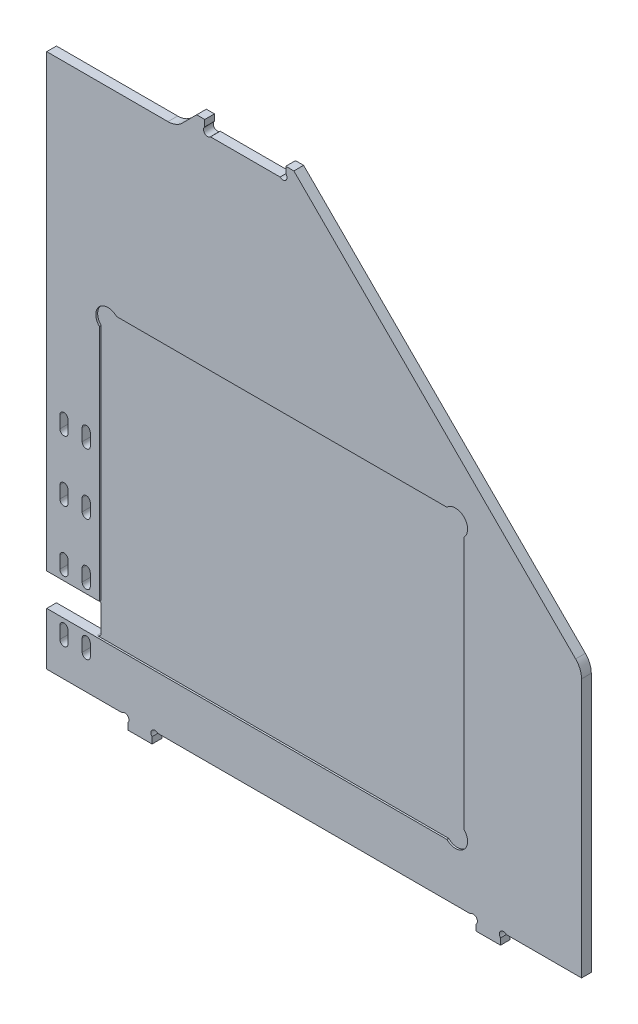
SolidWorks part; units mm, degrees
ref_plane "Front Plane" through (0, 0, 0) normal (0, 0, 1) x (1, 0, 0)
ref_plane "Top Plane" through (0, 0, 0) normal (0, 1, 0) x (1, 0, 0)
ref_plane "Right Plane" through (0, 0, 0) normal (1, 0, 0) x (0, 0, -1)
sketch "Sketch1" plane through (0, 0, 0) normal (0, 0, 1) x (1, 0, 0)
  line L2 (0, 66) -> (0, -66) construction
  line L3 (66, 66) -> (-66, 66)
  line L4 (66, 66) -> (66, -66)
  line L5 (66, -66) -> (-66, -66)
  line L6 (-66, 66) -> (-66, -66)
  line L7 (66, 66) -> (-66, -66) construction
  line L8 (66, -66) -> (-66, 66) construction
  line L9 (0, 66) -> (66, 0)
  line L10 (0, 66) -> (-7, 73)
  line L11 (-7, 73) -> (-27, 73)
  line L12 (-27, 73) -> (-34, 66)
  line L13 (-32, 68) -> (-2, 68)
  line L14 (39.2929, -66.7071) -> (40, -66) construction
  line L15 (46, -66) -> (40, -66)
  line L16 (46, -66) -> (46, -69)
  line L17 (46, -69) -> (40, -69)
  line L18 (40, -66) -> (40, -69)
  line L19 (43, -69) -> (43, -66) construction
  line L20 (-46, -66) -> (-46, -69)
  line L21 (-46, -66) -> (-40, -66)
  line L22 (-40, -66) -> (-40, -69)
  line L23 (-46, -69) -> (-40, -69)
  line L24 (-17, 73) -> (-17, 66) construction
  line L25 (-7, 71) -> (-5, 71)
  line L26 (-27, 71) -> (-7, 71)
  line L27 (-27, 71) -> (-27, 68)
  line L28 (-27, 68) -> (-7, 68)
  line L29 (-7, 71) -> (-7, 68)
  line L30 (-27, 71) -> (-7, 68) construction
  line L31 (-27, 68) -> (-7, 71) construction
  line L33 (-27, 71) -> (-29, 71)
  line L35 (-26.2929, 68.7071) -> (-27, 68) construction
  circle A0 centre (39.2929, -66.7071) radius 1
  circle A1 centre (46.7071, -66.7071) radius 1
  circle A2 centre (-46.7071, -66.7071) radius 1
  circle A3 centre (-39.2929, -66.7071) radius 1
  circle A4 centre (-26.2929, 68.7071) radius 1
  circle A5 centre (-7.7071, 68.7071) radius 1
  point P0 (0, 0)
  point P33 (-17, 69.5)
  dimension "D9" = 2
  dimension "D11" = 2
  dimension "D2" = 3
  dimension "D1" = 132
  dimension "D3" = 45
  dimension "D4" = 7
  dimension "D5" = 20
  dimension "D6" = 2
  dimension "D7" = 6
  dimension "D8" = 20
  dimension "D10" = 3
extrude "Boss-Extrude1" add sketch "Sketch1" along normal blind 2.4 contours L9 L3 L6 L5 L4 | L13 L12 L3 L10 | L22 A3 L5 A2 L20 L23 | L16 A1 L5 A0 L18 L17 | L27 L33 L12 L13 | L25 L29 L13 L10 region at (-6.2862, -6.2813, 0) region at (-17, 66.971, 0) region at (-5.0943, 69.3019, 0) region at (-28.9057, 69.3019, 0) region at (43, -67.526, 0) region at (-43, -67.526, 0)
sketch "Sketch3" plane through (0, 0, 2.4) normal (0, 0, 1) x (1, 0, 0)
  line L0 (-34, 66) -> (-66, 66) construction
  line L1 (-60.75, 66) -> (-57.25, 66)
  line L2 (-60.75, 66) -> (-60.75, -66)
  line L3 (-60.75, -66) -> (-57.25, -66)
  line L4 (-57.25, 66) -> (-57.25, -66)
  line L5 (-60.75, 66) -> (-57.25, -66) construction
  line L6 (-60.75, -66) -> (-57.25, 66) construction
  line L7 (-47.4142, -66) -> (-66, -66) construction
  line L8 (-59, 66) -> (-59, -66) construction
  line L9 (-66, 66) -> (-66, -66) construction
  line L10 (-61.75, -55) -> (-61.75, -58) construction
  line L11 (-60.75, -55) -> (-60.75, -58)
  line L12 (-62.75, -55) -> (-62.75, -58)
  line L13 (-56.25, -55) -> (-56.25, -58) construction
  line L14 (-57.25, -55) -> (-57.25, -58)
  line L15 (-55.25, -55) -> (-55.25, -58)
  line L16 (-61.75, -40) -> (-61.75, -43) construction
  line L17 (-60.75, -40) -> (-60.75, -43)
  line L18 (-62.75, -40) -> (-62.75, -43)
  line L19 (-56.25, -40) -> (-56.25, -43) construction
  line L20 (-57.25, -40) -> (-57.25, -43)
  line L21 (-55.25, -40) -> (-55.25, -43)
  line L22 (-61.75, -25) -> (-61.75, -28) construction
  line L23 (-60.75, -25) -> (-60.75, -28)
  line L24 (-62.75, -25) -> (-62.75, -28)
  line L25 (-56.25, -25) -> (-56.25, -28) construction
  line L26 (-57.25, -25) -> (-57.25, -28)
  line L27 (-55.25, -25) -> (-55.25, -28)
  line L28 (-61.75, -10) -> (-61.75, -13) construction
  line L29 (-60.75, -10) -> (-60.75, -13)
  line L30 (-62.75, -10) -> (-62.75, -13)
  line L31 (-56.25, -10) -> (-56.25, -13) construction
  line L32 (-57.25, -10) -> (-57.25, -13)
  line L33 (-55.25, -10) -> (-55.25, -13)
  arc A0 (-60.75, -55) -> (-62.75, -55) centre (-61.75, -55) ccw
  arc A1 (-62.75, -58) -> (-60.75, -58) centre (-61.75, -58) ccw
  arc A2 (-57.25, -55) -> (-55.25, -55) centre (-56.25, -55) cw
  arc A3 (-55.25, -58) -> (-57.25, -58) centre (-56.25, -58) cw
  arc A4 (-60.75, -40) -> (-62.75, -40) centre (-61.75, -40) ccw
  arc A5 (-62.75, -43) -> (-60.75, -43) centre (-61.75, -43) ccw
  arc A6 (-57.25, -40) -> (-55.25, -40) centre (-56.25, -40) cw
  arc A7 (-55.25, -43) -> (-57.25, -43) centre (-56.25, -43) cw
  arc A8 (-60.75, -25) -> (-62.75, -25) centre (-61.75, -25) ccw
  arc A9 (-62.75, -28) -> (-60.75, -28) centre (-61.75, -28) ccw
  arc A10 (-57.25, -25) -> (-55.25, -25) centre (-56.25, -25) cw
  arc A11 (-55.25, -28) -> (-57.25, -28) centre (-56.25, -28) cw
  arc A12 (-60.75, -10) -> (-62.75, -10) centre (-61.75, -10) ccw
  arc A13 (-62.75, -13) -> (-60.75, -13) centre (-61.75, -13) ccw
  arc A14 (-57.25, -10) -> (-55.25, -10) centre (-56.25, -10) cw
  arc A15 (-55.25, -13) -> (-57.25, -13) centre (-56.25, -13) cw
  point P0 (-59, 0)
  point P15 (-61.75, -56.5)
  point P23 (-56.25, -56.5)
  point P31 (-61.75, -41.5)
  point P38 (-56.25, -41.5)
  point P45 (-61.75, -26.5)
  point P52 (-56.25, -26.5)
  point P57 (-61.75, -11.5)
  point P64 (-56.25, -11.5)
  dimension "D1" = 3.5
  dimension "D2" = 7
  dimension "D3" = 2
  dimension "D4" = 3
  dimension "D5" = 9.5
  dimension "D7" = 15
  dimension "D6" = 4
extrude "Cut-Extrude1" cut sketch "Sketch3" against normal up to next contours L12 A1 L2 A0 | A3 L15 A2 L4 | A7 L21 A6 L4 | L18 A5 L2 A4 | L24 A9 L2 A8 | A11 L27 A10 L4 | L30 A13 L2 A12 | A15 L33 A14 L4 region at (-61.75, -11.5, 2.4) region at (-56.25, -11.5, 2.4) region at (-61.75, -26.5, 2.4) region at (-56.25, -26.5, 2.4) region at (-61.75, -41.5, 2.4) region at (-56.25, -41.5, 2.4) region at (-61.75, -56.5, 2.4) region at (-56.25, -56.5, 2.4)
sketch "Sketch4" plane through (0, 0, 2.4) normal (0, 0, 1) x (1, 0, 0)
  line L0 (-66, 66) -> (-66, -66) construction
  line L1 (-53, -53) -> (37, -53)
  line L2 (-53, -53) -> (-53, 18)
  line L3 (-53, 18) -> (37, 18)
  line L4 (37, -53) -> (37, 18)
  line L5 (-47.4142, -66) -> (-66, -66) construction
  line L6 (-50.8787, 15.8787) -> (-53, 18) construction
  line L7 (-53, -53) -> (-66, -53)
  line L8 (-53, -53) -> (-53, -45)
  line L9 (-53, -45) -> (-66, -45)
  line L10 (-66, -53) -> (-66, -45)
  line L11 (-8, 18) -> (-8, -53) construction
  line L12 (37, -17.5) -> (-53, -17.5) construction
  circle A0 centre (-50.8787, 15.8787) radius 3
  circle A1 centre (34.8787, 15.8787) radius 3
  circle A2 centre (34.8787, -50.8787) radius 3
  dimension "D6" = 6
  dimension "D1" = 90
  dimension "D2" = 71
  dimension "D3" = 13
  dimension "D4" = 13
  dimension "D5" = 8
extrude "Cut-Extrude2" cut sketch "Sketch4" against normal blind 0.45 contours L10 L7 L2 L9 | L1 L4 L3 L2 | A0 | A1 | A2 region at (-8.156, -17.6212, 2.4) region at (-59.5, -49, 2.4)
sketch "Sketch5" plane through (0, 0, 1.95) normal (0, 0, 1) x (1, 0, 0)
  line L0 (32.7574, -53) -> (-66, -53) construction
  line L1 (-66, -45) -> (-54, -45)
  line L2 (-66, -45) -> (-66, -53)
  line L3 (-66, -53) -> (-54, -53)
  line L4 (-53, -46) -> (-53, -52)
  line L5 (-53, -45) -> (-53, 13.7574) construction
  arc A0 (-54, -53) -> (-53, -52) centre (-54, -52) ccw
  arc A1 (-54, -45) -> (-53, -46) centre (-54, -46) cw
  point P11 (-53, -53)
  dimension "D1" = 1
extrude "Cut-Extrude3" cut sketch "Sketch5" against normal up to next
fillet "Fillet1" radius 5 2 edges at (66, 0, 1.2) (-34, 66, 1.2)
sketch "Sketch6" [suppressed] plane through (0, 0, 0) normal (0, 0, -1) x (-1, 0, 0)
  line L0 (66, 66) -> (66, -66) construction
  line L1 (46, -53) -> (-44, -53)
  line L2 (46, -53) -> (46, 18)
  line L3 (46, 18) -> (-44, 18)
  line L4 (-44, -53) -> (-44, 18)
  line L5 (47.4142, -66) -> (66, -66) construction
  line L6 (-41.8787, 15.8787) -> (-44, 18) construction
  line L7 (-44, -53) -> (-56, -53)
  line L8 (-44, -53) -> (-44, -45)
  line L9 (-44, -45) -> (-56, -45)
  line L10 (-57, -52) -> (-57, -46)
  line L11 (1, 18) -> (1, -53) construction
  line L12 (-44, -17.5) -> (46, -17.5) construction
  circle A0 centre (-41.8787, 15.8787) radius 3
  circle A1 centre (43.8787, 15.8787) radius 3
  circle A2 centre (43.8787, -50.8787) radius 3
  arc A3 (-56, -45) -> (-57, -46) centre (-56, -46) ccw
  arc A4 (-56, -53) -> (-57, -52) centre (-56, -52) cw
  point P23 (-57, -45)
  point P26 (-57, -53)
  dimension "D7" = 6
  dimension "D8" = 1
  dimension "D1" = 71
  dimension "D2" = 90
  dimension "D3" = 20
  dimension "D4" = 13
  dimension "D5" = 8
  dimension "D6" = 13
extrude "Cut-Extrude4" [suppressed] cut sketch "Sketch6" against normal blind 0.45 contours A2 L2 A1 L3 A0 L4 L1 | A4 L7 L4 L9 A3 L10 | A0 | A1 | A2
sketch "Sketch7" [suppressed] plane through (0, 0, 0.45) normal (0, 0, -1) x (-1, 0, 0)
  line L1 (-45, -45) -> (-57, -45)
  line L2 (-44, -46) -> (-44, -52)
  line L3 (-45, -53) -> (-57, -53)
  line L4 (-57, -45) -> (-57, -53)
  line L6 (46, -48.7574) -> (46, 13.7574)
  line L7 (41.7574, 18) -> (-39.7574, 18)
  line L8 (-44, 13.7574) -> (-44, -45)
  line L9 (-44, -45) -> (-56, -45)
  line L10 (-57, -46) -> (-57, -52)
  line L11 (-56, -53) -> (41.7574, -53)
  line L12 (46, -48.7574) -> (46, 13.7574)
  line L13 (41.7574, 18) -> (-39.7574, 18)
  line L14 (-44, 13.7574) -> (-44, -45)
  line L15 (-44, -45) -> (-56, -45)
  line L16 (-57, -46) -> (-57, -52)
  line L17 (-56, -53) -> (41.7574, -53)
  arc A0 (-44, -46) -> (-45, -45) centre (-45, -46) ccw
  arc A1 (-44, -52) -> (-45, -53) centre (-45, -52) cw
  arc A5 (46, 13.7574) -> (41.7574, 18) centre (43.8787, 15.8787) ccw
  arc A6 (-39.7574, 18) -> (-44, 13.7574) centre (-41.8787, 15.8787) ccw
  arc A7 (-56, -45) -> (-57, -46) centre (-56, -46) ccw
  arc A8 (-57, -52) -> (-56, -53) centre (-56, -52) ccw
  arc A9 (41.7574, -53) -> (46, -48.7574) centre (43.8787, -50.8787) ccw
  arc A10 (46, 13.7574) -> (41.7574, 18) centre (43.8787, 15.8787) ccw
  arc A11 (-39.7574, 18) -> (-44, 13.7574) centre (-41.8787, 15.8787) ccw
  arc A12 (-56, -45) -> (-57, -46) centre (-56, -46) ccw
  arc A13 (-57, -52) -> (-56, -53) centre (-56, -52) ccw
  arc A14 (41.7574, -53) -> (46, -48.7574) centre (43.8787, -50.8787) ccw
  dimension "D2" = 1
  dimension "D1" = 0
extrude "Cut-Extrude5" [suppressed] cut sketch "Sketch7" against normal up to next
